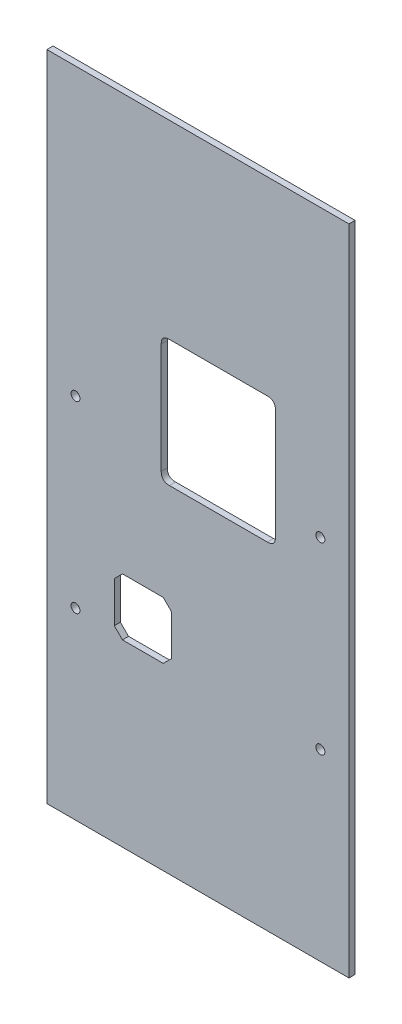
SolidWorks part; units mm, degrees
ref_plane "Plan de face" through (0, 0, 0) normal (0, 0, 1) x (1, 0, 0)
ref_plane "Plan de dessus" through (0, 0, 0) normal (0, 1, 0) x (1, 0, 0)
ref_plane "Plan de droite" through (0, 0, 0) normal (1, 0, 0) x (0, 0, -1)
sketch "Esquisse1" plane through (0, 0, 0) normal (0, 0, 1) x (1, 0, 0)
  line L0 (0, 0) -> (74, 0) construction
  line L1 (0, 0) -> (-74, 0) construction
  line L2 (-74, 0) -> (-74, 165) construction
  line L3 (-74, 165) -> (74, 165)
  line L4 (74, 165) -> (74, -165)
  line L5 (74, -165) -> (-74, -165)
  line L7 (-74, 165) -> (-74, -165)
  dimension "D1" = 165
  dimension "D2" = 74
  dimension "D4" = 330
  dimension "D5" = 330
extrude "Boss.-Extru.1" add sketch "Esquisse1" along normal blind 3
sketch "Esquisse3" plane through (0, 0, 3) normal (0, 0, 1) x (1, 0, 0)
  line L0 (-60, -165) -> (60, -165) construction
  line L1 (-74, -165) -> (74, -165) construction
  line L2 (60, -165) -> (60, -75) construction
  line L3 (0, -1.65) -> (0, 1.65) construction
  line L6 (-60, -165) -> (0, -165) construction
  line L7 (60, -75) -> (60, 15) construction
  circle A0 centre (60, -75) radius 2.2
  circle A3 centre (60, 15) radius 2.2
  point P10 (0, -165)
  dimension "D3" = 60
  dimension "D4" = 90
  dimension "D1" = 60
  dimension "D2" = 90
extrude "Enlèv. mat.-Extru.2" cut sketch "Esquisse3" against normal up to next
sketch "Esquisse4" plane through (0, 0, 3) normal (0, 0, 1) x (1, 0, 0)
  line L0 (-74, 165) -> (-74, 155)
  line L1 (-74, 165) -> (-74, -165) construction
  line L2 (-74, 155) -> (74, 155)
  line L3 (74, -165) -> (74, 165) construction
  line L4 (74, 155) -> (74, 165)
  line L5 (74, 165) -> (-74, 165)
extrude "Enlèv. mat.-Extru.3" cut sketch "Esquisse4" against normal up to next
sketch "Esquisse5" plane through (0, 0, 3) normal (0, 0, 1) x (1, 0, 0)
  line L0 (0, -165) -> (0, 0) construction
  line L1 (-74, -165) -> (74, -165) construction
  line L2 (0, 0) -> (0, 62) construction
  line L3 (0, 0) -> (38, 0)
  line L4 (38, 0) -> (38, 62)
  line L7 (38, 62) -> (-18, 62)
  line L8 (-18, 62) -> (-18, 0)
  line L9 (-18, 0) -> (0, 0)
  dimension "D4" = 56
  dimension "D1" = 165
  dimension "D2" = 62
  dimension "D3" = 38
extrude "Enlèv. mat.-Extru.4" cut sketch "Esquisse5" against normal up to next
fillet "Congé1" radius 4 4 edges at (38, 62, 1.5) (-18, 62, 1.5) (-18, 0, 1.5) (38, 0, 1.5) conic rho 0.5
sketch "Esquisse6" plane through (0, 0, 0) normal (0, 0, -1) x (-1, 0, 0)
  line L0 (74, -165) -> (60, -165) construction
  line L1 (74, -165) -> (-74, -165) construction
  line L2 (60, -165) -> (60, -63) construction
  line L3 (60, -63) -> (27, -63) construction
  line L4 (27, -77) -> (27, -49) construction
  line L6 (17, -49) -> (37, -49)
  line L7 (37, -49) -> (41, -49) construction
  line L27 (41, -49) -> (41, -53) construction
  line L28 (41, -53) -> (41, -73)
  line L33 (37, -49) -> (41, -53)
  line L34 (41, -77) -> (41, -73) construction
  line L35 (37, -77) -> (41, -77) construction
  line L36 (37, -77) -> (41, -73)
  line L41 (17, -77) -> (37, -77)
  line L42 (17, -77) -> (13, -77) construction
  line L43 (13, -77) -> (13, -73) construction
  line L44 (13, -49) -> (13, -53) construction
  line L45 (17, -49) -> (13, -49) construction
  line L46 (17, -77) -> (13, -73)
  line L47 (17, -49) -> (13, -53)
  line L48 (13, -53) -> (13, -73)
  point P16 (41, -63)
  point P22 (13, -63)
  dimension "D1" = 102
  dimension "D2" = 14
  dimension "D3" = 4
  dimension "D4" = 28
  dimension "D5" = 4
  dimension "D6" = 33
  dimension "D7" = 14
  dimension "D8" = 28
extrude "Enlèv. mat.-Extru.5" cut sketch "Esquisse6" against normal up to next
mirror "Symétrie1" about plane through (0, 0, 0) normal (1, 0, 0) of "Enlèv. mat.-Extru.2"
